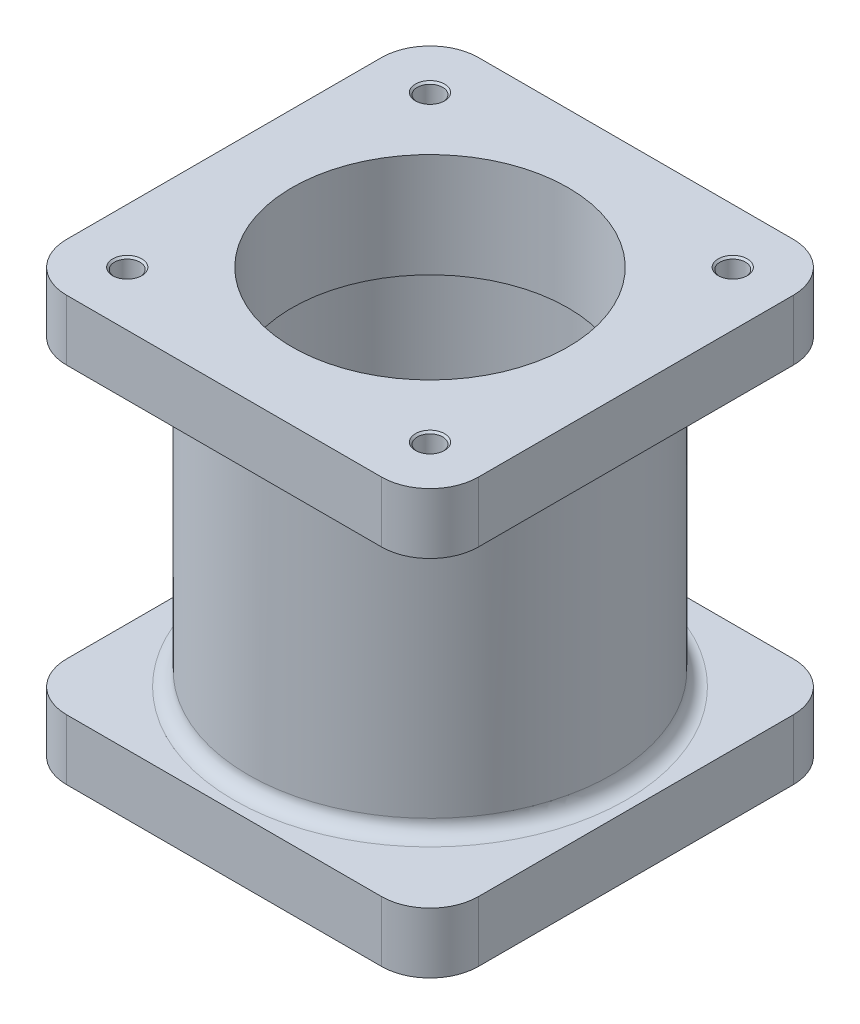
SolidWorks part; units mm, degrees
material "1060 Сплав"
ref_plane "Спереди" through (0, 0, 0) normal (0, 0, 1) x (1, 0, 0)
ref_plane "Сверху" through (0, 0, 0) normal (0, 1, 0) x (1, 0, 0)
ref_plane "Справа" through (0, 0, 0) normal (1, 0, 0) x (0, 0, -1)
sketch "Эскиз1" plane through (0, 0, 0) normal (0, 1, 0) x (1, 0, 0)
  line L0 (0, -1490.4115) -> (0, 73030.1655) construction
  line L2 (-1490.4115, 0) -> (73030.1655, 0) construction
  line L3 (-65, -85) -> (65, -85)
  line L4 (-85, -65) -> (-85, 65)
  line L5 (-65, 85) -> (65, 85)
  line L6 (85, -65) -> (85, 65)
  line L7 (-85, -85) -> (85, 85) construction
  line L8 (-85, 85) -> (85, -85) construction
  arc A0 (-85, -65) -> (-65, -85) centre (-65, -65) ccw
  arc A1 (65, -85) -> (85, -65) centre (65, -65) ccw
  arc A2 (85, 65) -> (65, 85) centre (65, 65) ccw
  arc A3 (-65, 85) -> (-85, 65) centre (-65, 65) ccw
  point P1 (0, 0)
  dimension "D2" = 20
  dimension "D1" = 170
extrude "Бобышка-Вытянуть1" add sketch "Эскиз1" along normal blind 25
ref_plane "Плоскость1" through (0, 87.5, 0) normal (0, 1, 0) x (1, 0, 0)
sketch "Эскиз7" plane through (0, 25, 0) normal (0, 1, 0) x (1, 0, 0)
  circle A0 centre (0, 0) radius 75
  dimension "D1" = 150
extrude "Бобышка-Вытянуть2" add sketch "Эскиз7" along normal blind 135
sketch "Эскиз14" plane through (0, 0, 0) normal (0, -1, 0) x (1, 0, 0)
  line L1 (-62.5, -62.5) -> (62.5, -62.5)
  line L2 (-62.5, -62.5) -> (-62.5, 62.5)
  line L3 (-62.5, 62.5) -> (62.5, 62.5)
  line L4 (62.5, -62.5) -> (62.5, 62.5)
  line L5 (-62.5, -62.5) -> (62.5, 62.5) construction
  line L6 (-62.5, 62.5) -> (62.5, -62.5) construction
  point P0 (0, 0)
  dimension "D1" = 125
  dimension "D2" = 125
hole_wizard "Отверстие обработанное метчиком M12x1.51" positions "Трехмерный эскиз1" profile "Эскиз15" tap size "M12x1.5" standard "Ansi Metric"
sketch3d "Трехмерный эскиз1"
  point P0 (-62.5, 0, -62.5)
  point P3 (-62.5, 0, 62.5)
  point P6 (62.5, 0, 62.5)
  point P9 (62.5, 0, -62.5)
sketch "Эскиз15" plane through (-62.5, 0, -62.5) normal (1, 0, 0) x (0, 0, -1)
  line L0 (0, 0) -> (0, 20.1545)
  line L1 (0, 20.1545) -> (5.25, 17)
  line L2 (5.25, 17) -> (5.25, 0.775)
  line L3 (5.25, 0.775) -> (6.025, 0)
  line L5 (6.025, 0) -> (0, 0)
  line L6 (-5.25, 0.775) -> (-6.025, 0) construction
  line L10 (0, 20.1545) -> (-5.25, 17) construction
  line L11 (0, -6.35) -> (0, 107.95) construction
  dimension "Диаметр сверла" = 10.5
  dimension "Глубина сверла" = 17
  dimension "Диаметр передней зенковки" = 12.05
  dimension "Угол передней зенковки" = 90
  dimension "Угол заточки сверла" = 118
cosmetic thread "Отверстие резьбы1" parameters "D1"=13, "D2"=12
cosmetic thread "Отверстие резьбы2" parameters "D1"=13, "D2"=12
cosmetic thread "Отверстие резьбы3" parameters "D1"=13, "D2"=12
cosmetic thread "Отверстие резьбы4" parameters "D1"=13, "D2"=12
sketch "Эскиз8" plane through (0, 0, 0) normal (0, -1, 0) x (1, 0, 0)
  circle A0 centre (0, 0) radius 65
  dimension "D1" = 130
extrude "Вырез-Вытянуть1" cut sketch "Эскиз8" against normal blind 132
mirror "Зеркальное отражение1" about plane through (0, 87.5, 0) normal (0, 1, 0) of "Отверстие обработанное метчиком M12x1.51", "Бобышка-Вытянуть1"
sketch "Эскиз9" plane through (0, 132, 0) normal (0, -1, 0) x (1, 0, 0)
  circle A0 centre (0, 0) radius 57
  dimension "D1" = 114
extrude "Вырез-Вытянуть2" cut sketch "Эскиз9" against normal up to next
sketch "Эскиз16" plane through (0, 0, -85) normal (0, 0, -1) x (-1, 0, 0)
  line L0 (0, 175) -> (0, 0) construction
  line L1 (-65, 175) -> (65, 175) construction
  line L2 (0, 115) -> (0, 175) construction
  line L3 (-18, 115) -> (-18, 175)
  line L4 (18, 115) -> (18, 175)
  line L5 (-18, 175) -> (18, 175)
  arc A0 (-18, 115) -> (18, 115) centre (0, 115) ccw
  arc A1 (18, 175) -> (-18, 175) centre (0, 175) ccw
  point P6 (0, 145)
  line M5 (-65, 150) -> (65, 150)
  dimension "D2" = 60
  dimension "D1" = 36
extrude "Бобышка-Вытянуть3" add sketch "Эскиз16" against normal up to body separate body contours L3 A0 L4 M5 region at (0, 125.2672, -85)
sketch "Эскиз17" plane through (0, 0, -85) normal (0, 0, -1) x (-1, 0, 0)
  line L0 (0, 115) -> (0, 151) construction
  line L1 (0, 151) -> (0, 175) construction
  line L2 (-65, 175) -> (65, 175) construction
  dimension "D1" = 36
hole_wizard "Отверстие обработанное метчиком M10x1.02" positions "Трехмерный эскиз2" profile "Эскиз18" tap size "M10x1.0" standard "Ansi Metric"
sketch3d "Трехмерный эскиз2"
  point P0 (0, 115, -85)
  point P3 (0, 151, -85)
sketch "Эскиз18" plane through (0, 115, -85) normal (1, 0, 0) x (0, 1, 0)
  line L0 (0, 0) -> (0, 15.7039)
  line L1 (0, 15.7039) -> (4.5, 13)
  line L2 (4.5, 13) -> (4.5, 0.525)
  line L3 (4.5, 0.525) -> (5.025, 0)
  line L5 (5.025, 0) -> (0, 0)
  line L6 (-4.5, 0.525) -> (-5.025, 0) construction
  line L10 (0, 15.7039) -> (-4.5, 13) construction
  line L11 (0, -6.35) -> (0, 107.95) construction
  dimension "Диаметр сверла" = 9
  dimension "Глубина сверла" = 13
  dimension "Диаметр передней зенковки" = 10.05
  dimension "Угол передней зенковки" = 90
  dimension "Угол заточки сверла" = 118
cosmetic thread "Отверстие резьбы5" parameters "D1"=10, "D2"=10
cosmetic thread "Отверстие резьбы6" parameters "D1"=10, "D2"=10
fillet "Скругление2" radius 6 4 edges at (0, 25, 75) (-18, 150, -78.904) (18, 150, -78.904) (0, 150, 75)
fillet "Скругление3" radius 3 5 edges at (-19.9576, 148.4339, -74.3247) (-18, 129.5, -72.808) (-1.8383, 97.0941, -74.9775) (19.9576, 148.4339, -74.3247) (18, 129.5, -72.808)
